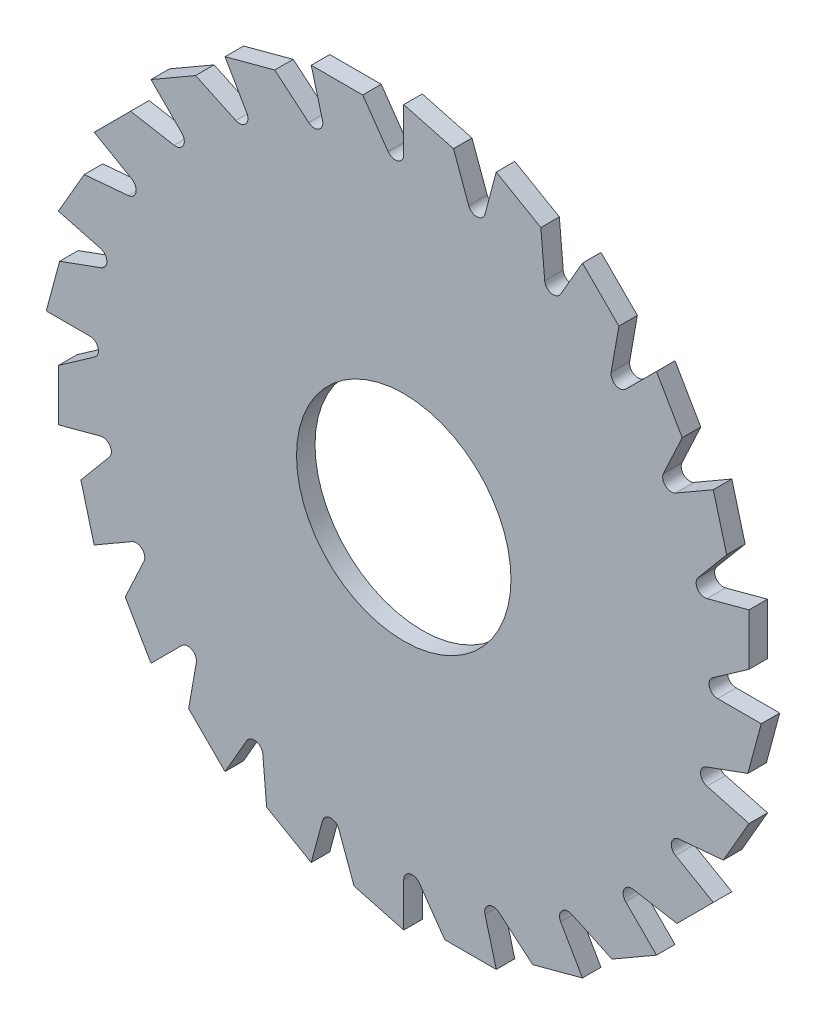
SolidWorks part; units mm, degrees
ref_plane "Front Plane" through (0, 0, 0) normal (0, 0, 1) x (1, 0, 0)
ref_plane "Top Plane" through (0, 0, 0) normal (0, 1, 0) x (1, 0, 0)
ref_plane "Right Plane" through (0, 0, 0) normal (1, 0, 0) x (0, 0, -1)
sketch "Sketch1" plane through (0, 0, 0) normal (0, 0, 1) x (1, 0, 0)
  line L0 (0, 31.75) -> (4.4162, 30.5667)
  line L1 (4.4162, 30.5667) -> (5.7634, 26.8652)
  line L2 (7.2155, 26.9286) -> (8.2175, 30.6681)
  line L3 (0, 31.75) -> (0, 0) construction
  line L4 (0, 0) -> (8.2175, 30.6681) construction
  line L5 (0, 31.75) -> (12.0811, 31.75) construction
  line L6 (6.3024, 26.3847) -> (0, 0) construction
  line L7 (6.3024, 26.3847) -> (4.0698, 26.918) construction
  line L8 (13.9393, 24.1436) -> (15.875, 27.4963)
  line L9 (12.177, 28.3821) -> (12.5203, 24.4581)
  line L10 (8.2175, 30.6681) -> (12.177, 28.3821)
  line L11 (19.7131, 19.7131) -> (22.4506, 22.4506)
  line L12 (19.1079, 24.2634) -> (18.4239, 20.3843)
  line L13 (15.875, 27.4963) -> (19.1079, 24.2634)
  line L14 (24.1436, 13.9393) -> (27.4963, 15.875)
  line L15 (24.7366, 18.4912) -> (23.072, 14.9212)
  line L16 (22.4506, 22.4506) -> (24.7366, 18.4912)
  line L17 (26.9286, 7.2155) -> (30.6681, 8.2175)
  line L18 (28.6796, 11.4588) -> (26.1477, 8.4413)
  line L19 (27.4963, 15.875) -> (28.6796, 11.4588)
  line L20 (27.8786, 0) -> (31.75, 0)
  line L21 (30.6681, 3.6455) -> (27.4415, 1.3862)
  line L22 (30.6681, 8.2175) -> (30.6681, 3.6455)
  line L23 (26.9286, -7.2155) -> (30.6681, -8.2175)
  line L24 (30.5667, -4.4162) -> (26.8652, -5.7634)
  line L25 (31.75, 0) -> (30.5667, -4.4162)
  line L26 (24.1436, -13.9393) -> (27.4963, -15.875)
  line L27 (28.3821, -12.177) -> (24.4581, -12.5203)
  line L28 (30.6681, -8.2175) -> (28.3821, -12.177)
  line L29 (19.7131, -19.7131) -> (22.4506, -22.4506)
  line L30 (24.2634, -19.1079) -> (20.3843, -18.4239)
  line L31 (27.4963, -15.875) -> (24.2634, -19.1079)
  line L32 (13.9393, -24.1436) -> (15.875, -27.4963)
  line L33 (18.4912, -24.7366) -> (14.9212, -23.072)
  line L34 (22.4506, -22.4506) -> (18.4912, -24.7366)
  line L35 (7.2155, -26.9286) -> (8.2175, -30.6681)
  line L36 (11.4588, -28.6796) -> (8.4413, -26.1477)
  line L37 (15.875, -27.4963) -> (11.4588, -28.6796)
  line L38 (0, -27.8786) -> (0, -31.75)
  line L39 (3.6455, -30.6681) -> (1.3862, -27.4415)
  line L40 (8.2175, -30.6681) -> (3.6455, -30.6681)
  line L41 (-7.2155, -26.9286) -> (-8.2175, -30.6681)
  line L42 (-4.4162, -30.5667) -> (-5.7634, -26.8652)
  line L43 (0, -31.75) -> (-4.4162, -30.5667)
  line L44 (-13.9393, -24.1436) -> (-15.875, -27.4963)
  line L45 (-12.177, -28.3821) -> (-12.5203, -24.4581)
  line L46 (-8.2175, -30.6681) -> (-12.177, -28.3821)
  line L47 (-19.7131, -19.7131) -> (-22.4506, -22.4506)
  line L48 (-19.1079, -24.2634) -> (-18.4239, -20.3843)
  line L49 (-15.875, -27.4963) -> (-19.1079, -24.2634)
  line L50 (-24.1436, -13.9393) -> (-27.4963, -15.875)
  line L51 (-24.7366, -18.4912) -> (-23.072, -14.9212)
  line L52 (-22.4506, -22.4506) -> (-24.7366, -18.4912)
  line L53 (-26.9286, -7.2155) -> (-30.6681, -8.2175)
  line L54 (-28.6796, -11.4588) -> (-26.1477, -8.4413)
  line L55 (-27.4963, -15.875) -> (-28.6796, -11.4588)
  line L56 (-27.8786, 0) -> (-31.75, 0)
  line L57 (-30.6681, -3.6455) -> (-27.4415, -1.3862)
  line L58 (-30.6681, -8.2175) -> (-30.6681, -3.6455)
  line L59 (-26.9286, 7.2155) -> (-30.6681, 8.2175)
  line L60 (-30.5667, 4.4162) -> (-26.8652, 5.7634)
  line L61 (-31.75, 0) -> (-30.5667, 4.4162)
  line L62 (-24.1436, 13.9393) -> (-27.4963, 15.875)
  line L63 (-28.3821, 12.177) -> (-24.4581, 12.5203)
  line L64 (-30.6681, 8.2175) -> (-28.3821, 12.177)
  line L65 (-19.7131, 19.7131) -> (-22.4506, 22.4506)
  line L66 (-24.2634, 19.1079) -> (-20.3843, 18.4239)
  line L67 (-27.4963, 15.875) -> (-24.2634, 19.1079)
  line L68 (-13.9393, 24.1436) -> (-15.875, 27.4963)
  line L69 (-18.4912, 24.7366) -> (-14.9212, 23.072)
  line L70 (-22.4506, 22.4506) -> (-18.4912, 24.7366)
  line L71 (-7.2155, 26.9286) -> (-8.2175, 30.6681)
  line L72 (-11.4588, 28.6796) -> (-8.4413, 26.1477)
  line L73 (-15.875, 27.4963) -> (-11.4588, 28.6796)
  line L74 (0, 27.8786) -> (0, 31.75)
  line L75 (-3.6455, 30.6681) -> (-1.3862, 27.4415)
  line L76 (-8.2175, 30.6681) -> (-3.6455, 30.6681)
  circle A0 centre (0, 0) radius 31.75 construction
  circle A1 centre (0, 0) radius 9.525
  circle A2 centre (0, 0) radius 27.127 construction
  arc A3 (5.7634, 26.8652) -> (7.2155, 26.9286) centre (6.4795, 27.1259) ccw
  arc A4 (12.5203, 24.4581) -> (13.9393, 24.1436) centre (13.2794, 24.5246) ccw
  arc A5 (18.4239, 20.3843) -> (19.7131, 19.7131) centre (19.1743, 20.2519) ccw
  arc A6 (23.072, 14.9212) -> (24.1436, 13.9393) centre (23.7626, 14.5992) ccw
  arc A7 (26.1477, 8.4413) -> (26.9286, 7.2155) centre (26.7314, 7.9515) ccw
  arc A8 (27.4415, 1.3862) -> (27.8786, 0) centre (27.8786, 0.762) ccw
  arc A9 (26.8652, -5.7634) -> (26.9286, -7.2155) centre (27.1259, -6.4795) ccw
  arc A10 (24.4581, -12.5203) -> (24.1436, -13.9393) centre (24.5246, -13.2794) ccw
  arc A11 (20.3843, -18.4239) -> (19.7131, -19.7131) centre (20.2519, -19.1743) ccw
  arc A12 (14.9212, -23.072) -> (13.9393, -24.1436) centre (14.5992, -23.7626) ccw
  arc A13 (8.4413, -26.1477) -> (7.2155, -26.9286) centre (7.9515, -26.7314) ccw
  arc A14 (1.3862, -27.4415) -> (0, -27.8786) centre (0.762, -27.8786) ccw
  arc A15 (-5.7634, -26.8652) -> (-7.2155, -26.9286) centre (-6.4795, -27.1259) ccw
  arc A16 (-12.5203, -24.4581) -> (-13.9393, -24.1436) centre (-13.2794, -24.5246) ccw
  arc A17 (-18.4239, -20.3843) -> (-19.7131, -19.7131) centre (-19.1743, -20.2519) ccw
  arc A18 (-23.072, -14.9212) -> (-24.1436, -13.9393) centre (-23.7626, -14.5992) ccw
  arc A19 (-26.1477, -8.4413) -> (-26.9286, -7.2155) centre (-26.7314, -7.9515) ccw
  arc A20 (-27.4415, -1.3862) -> (-27.8786, 0) centre (-27.8786, -0.762) ccw
  arc A21 (-26.8652, 5.7634) -> (-26.9286, 7.2155) centre (-27.1259, 6.4795) ccw
  arc A22 (-24.4581, 12.5203) -> (-24.1436, 13.9393) centre (-24.5246, 13.2794) ccw
  arc A23 (-20.3843, 18.4239) -> (-19.7131, 19.7131) centre (-20.2519, 19.1743) ccw
  arc A24 (-14.9212, 23.072) -> (-13.9393, 24.1436) centre (-14.5992, 23.7626) ccw
  arc A25 (-8.4413, 26.1477) -> (-7.2155, 26.9286) centre (-7.9515, 26.7314) ccw
  arc A26 (-1.3862, 27.4415) -> (0, 27.8786) centre (-0.762, 27.8786) ccw
  dimension "D1" = 63.5
  dimension "D2" = 19.05
  dimension "D3" = 125
  dimension "D7" = 0.762
  dimension "D4" = 15
  dimension "D5" = 15
  dimension "D6" = 4.572
  dimension "D8" = 24
extrude "Boss-Extrude1" add sketch "Sketch1" along normal blind 1.6444 contours A26 L75 L76 L71 A25 L72 L73 L68 A24 L69 L70 L65 A23 L66 L67 L62 A22 L63 L64 L59 A21 L60 L61 L56 A20 L57 L58 L53 A19 L54 L55 L50 A18 L51 L52 L47 A17 L48 L49 L44 A16 L45 L46 L41 A15 L42 L43 L38 A14 L39 L40 region at (1.9757, 30.2909, 0)
ref_plane "Plane1" through (0, 0, 0.8222) normal (0, 0, 1) x (1, 0, 0)
sketch "Sketch2" plane through (0, 0, 0) normal (0, 0, 1) x (1, 0, 0)
  line L0 (31.75, -31.75) -> (31.75, 31.75)
  line L1 (400.05, -31.75) -> (-31.75, -31.75)
  line L2 (400.05, -31.75) -> (400.05, 400.05)
  line L3 (400.05, 400.05) -> (-31.75, 400.05)
  line L4 (-31.75, -31.75) -> (-31.75, 400.05)
  line L5 (184.15, 400.05) -> (184.15, -31.75) construction
  line L6 (400.05, 184.15) -> (-31.75, 184.15) construction
  line L7 (-31.75, -31.75) -> (31.75, -31.75)
  line L8 (-31.75, -31.75) -> (-31.75, 31.75)
  line L9 (-31.75, 31.75) -> (31.75, 31.75)
  line L10 (31.75, -31.75) -> (31.75, 31.75)
  line L11 (0, 31.75) -> (0, -31.75) construction
  line L12 (-31.75, 0) -> (31.75, 0) construction
  line L13 (31.75, -31.75) -> (95.25, -31.75)
  line L14 (95.25, -31.75) -> (95.25, 31.75)
  line L15 (31.75, 31.75) -> (95.25, 31.75)
  line L16 (95.25, -31.75) -> (95.25, 31.75)
  line L17 (95.25, -31.75) -> (158.75, -31.75)
  line L18 (158.75, -31.75) -> (158.75, 31.75)
  line L19 (95.25, 31.75) -> (158.75, 31.75)
  line L20 (158.75, -31.75) -> (158.75, 31.75)
  line L21 (158.75, -31.75) -> (222.25, -31.75)
  line L22 (222.25, -31.75) -> (222.25, 31.75)
  line L23 (158.75, 31.75) -> (222.25, 31.75)
  line L24 (222.25, -31.75) -> (222.25, 31.75)
  line L25 (222.25, -31.75) -> (285.75, -31.75)
  line L26 (285.75, -31.75) -> (285.75, 31.75)
  line L27 (222.25, 31.75) -> (285.75, 31.75)
  line L28 (285.75, -31.75) -> (285.75, 31.75)
  line L29 (285.75, -31.75) -> (349.25, -31.75)
  line L30 (349.25, -31.75) -> (349.25, 31.75)
  line L31 (285.75, 31.75) -> (349.25, 31.75)
  line L32 (31.75, 31.75) -> (31.75, 95.25)
  line L33 (31.75, 31.75) -> (95.25, 31.75)
  line L34 (95.25, 31.75) -> (95.25, 95.25)
  line L35 (31.75, 95.25) -> (95.25, 95.25)
  line L36 (95.25, 31.75) -> (95.25, 95.25)
  line L37 (95.25, 31.75) -> (158.75, 31.75)
  line L38 (158.75, 31.75) -> (158.75, 95.25)
  line L39 (95.25, 95.25) -> (158.75, 95.25)
  line L40 (158.75, 31.75) -> (158.75, 95.25)
  line L41 (158.75, 31.75) -> (222.25, 31.75)
  line L42 (222.25, 31.75) -> (222.25, 95.25)
  line L43 (158.75, 95.25) -> (222.25, 95.25)
  line L44 (222.25, 31.75) -> (222.25, 95.25)
  line L45 (222.25, 31.75) -> (285.75, 31.75)
  line L46 (285.75, 31.75) -> (285.75, 95.25)
  line L47 (222.25, 95.25) -> (285.75, 95.25)
  line L48 (285.75, 31.75) -> (285.75, 95.25)
  line L49 (285.75, 31.75) -> (349.25, 31.75)
  line L50 (349.25, 31.75) -> (349.25, 95.25)
  line L51 (285.75, 95.25) -> (349.25, 95.25)
  line L52 (31.75, 95.25) -> (31.75, 158.75)
  line L53 (31.75, 95.25) -> (95.25, 95.25)
  line L54 (95.25, 95.25) -> (95.25, 158.75)
  line L55 (31.75, 158.75) -> (95.25, 158.75)
  line L56 (95.25, 95.25) -> (95.25, 158.75)
  line L57 (95.25, 95.25) -> (158.75, 95.25)
  line L58 (158.75, 95.25) -> (158.75, 158.75)
  line L59 (95.25, 158.75) -> (158.75, 158.75)
  line L60 (158.75, 95.25) -> (158.75, 158.75)
  line L61 (158.75, 95.25) -> (222.25, 95.25)
  line L62 (222.25, 95.25) -> (222.25, 158.75)
  line L63 (158.75, 158.75) -> (222.25, 158.75)
  line L64 (222.25, 95.25) -> (222.25, 158.75)
  line L65 (222.25, 95.25) -> (285.75, 95.25)
  line L66 (285.75, 95.25) -> (285.75, 158.75)
  line L67 (222.25, 158.75) -> (285.75, 158.75)
  line L68 (285.75, 95.25) -> (285.75, 158.75)
  line L69 (285.75, 95.25) -> (349.25, 95.25)
  line L70 (349.25, 95.25) -> (349.25, 158.75)
  line L71 (285.75, 158.75) -> (349.25, 158.75)
  line L72 (31.75, 158.75) -> (31.75, 222.25)
  line L73 (31.75, 158.75) -> (95.25, 158.75)
  line L74 (95.25, 158.75) -> (95.25, 222.25)
  line L75 (31.75, 222.25) -> (95.25, 222.25)
  line L76 (95.25, 158.75) -> (95.25, 222.25)
  line L77 (95.25, 158.75) -> (158.75, 158.75)
  line L78 (158.75, 158.75) -> (158.75, 222.25)
  line L79 (95.25, 222.25) -> (158.75, 222.25)
  line L80 (158.75, 158.75) -> (158.75, 222.25)
  line L81 (158.75, 158.75) -> (222.25, 158.75)
  line L82 (222.25, 158.75) -> (222.25, 222.25)
  line L83 (158.75, 222.25) -> (222.25, 222.25)
  line L84 (222.25, 158.75) -> (222.25, 222.25)
  line L85 (222.25, 158.75) -> (285.75, 158.75)
  line L86 (285.75, 158.75) -> (285.75, 222.25)
  line L87 (222.25, 222.25) -> (285.75, 222.25)
  line L88 (285.75, 158.75) -> (285.75, 222.25)
  line L89 (285.75, 158.75) -> (349.25, 158.75)
  line L90 (349.25, 158.75) -> (349.25, 222.25)
  line L91 (285.75, 222.25) -> (349.25, 222.25)
  line L92 (31.75, 222.25) -> (31.75, 285.75)
  line L93 (31.75, 222.25) -> (95.25, 222.25)
  line L94 (95.25, 222.25) -> (95.25, 285.75)
  line L95 (31.75, 285.75) -> (95.25, 285.75)
  line L96 (95.25, 222.25) -> (95.25, 285.75)
  line L97 (95.25, 222.25) -> (158.75, 222.25)
  line L98 (158.75, 222.25) -> (158.75, 285.75)
  line L99 (95.25, 285.75) -> (158.75, 285.75)
  line L100 (158.75, 222.25) -> (158.75, 285.75)
  line L101 (158.75, 222.25) -> (222.25, 222.25)
  line L102 (222.25, 222.25) -> (222.25, 285.75)
  line L103 (158.75, 285.75) -> (222.25, 285.75)
  line L104 (222.25, 222.25) -> (222.25, 285.75)
  line L105 (222.25, 222.25) -> (285.75, 222.25)
  line L106 (285.75, 222.25) -> (285.75, 285.75)
  line L107 (222.25, 285.75) -> (285.75, 285.75)
  line L108 (285.75, 222.25) -> (285.75, 285.75)
  line L109 (285.75, 222.25) -> (349.25, 222.25)
  line L110 (349.25, 222.25) -> (349.25, 285.75)
  line L111 (285.75, 285.75) -> (349.25, 285.75)
  line L112 (31.75, 285.75) -> (31.75, 349.25)
  line L113 (31.75, 285.75) -> (95.25, 285.75)
  line L114 (95.25, 285.75) -> (95.25, 349.25)
  line L115 (31.75, 349.25) -> (95.25, 349.25)
  line L116 (95.25, 285.75) -> (95.25, 349.25)
  line L117 (95.25, 285.75) -> (158.75, 285.75)
  line L118 (158.75, 285.75) -> (158.75, 349.25)
  line L119 (95.25, 349.25) -> (158.75, 349.25)
  line L120 (158.75, 285.75) -> (158.75, 349.25)
  line L121 (158.75, 285.75) -> (222.25, 285.75)
  line L122 (222.25, 285.75) -> (222.25, 349.25)
  line L123 (158.75, 349.25) -> (222.25, 349.25)
  line L124 (222.25, 285.75) -> (222.25, 349.25)
  line L125 (222.25, 285.75) -> (285.75, 285.75)
  line L126 (285.75, 285.75) -> (285.75, 349.25)
  line L127 (222.25, 349.25) -> (285.75, 349.25)
  line L128 (285.75, 285.75) -> (285.75, 349.25)
  line L129 (285.75, 285.75) -> (349.25, 285.75)
  line L130 (349.25, 285.75) -> (349.25, 349.25)
  line L131 (285.75, 349.25) -> (349.25, 349.25)
  line L132 (-31.75, 31.75) -> (-31.75, 95.25)
  line L133 (-31.75, 31.75) -> (31.75, 31.75)
  line L134 (31.75, 31.75) -> (31.75, 95.25)
  line L135 (-31.75, 95.25) -> (31.75, 95.25)
  line L136 (-31.75, 95.25) -> (-31.75, 158.75)
  line L137 (-31.75, 95.25) -> (31.75, 95.25)
  line L138 (31.75, 95.25) -> (31.75, 158.75)
  line L139 (-31.75, 158.75) -> (31.75, 158.75)
  line L140 (-31.75, 158.75) -> (-31.75, 222.25)
  line L141 (-31.75, 158.75) -> (31.75, 158.75)
  line L142 (31.75, 158.75) -> (31.75, 222.25)
  line L143 (-31.75, 222.25) -> (31.75, 222.25)
  line L144 (-31.75, 222.25) -> (-31.75, 285.75)
  line L145 (-31.75, 222.25) -> (31.75, 222.25)
  line L146 (31.75, 222.25) -> (31.75, 285.75)
  line L147 (-31.75, 285.75) -> (31.75, 285.75)
  line L148 (-31.75, 285.75) -> (-31.75, 349.25)
  line L149 (-31.75, 285.75) -> (31.75, 285.75)
  line L150 (31.75, 285.75) -> (31.75, 349.25)
  line L151 (-31.75, 349.25) -> (31.75, 349.25)
  line L152 (-31.75, -31.75) -> (31.75, -31.75) construction
  line L153 (-31.75, -31.75) -> (-31.75, 31.75) construction
  line L155 (-31.75, 400.05) -> (57.15, 400.05)
  line L156 (-31.75, 400.05) -> (-31.75, 349.25)
  line L157 (-31.75, 349.25) -> (57.15, 349.25)
  line L158 (57.15, 400.05) -> (57.15, 349.25)
  line L159 (57.15, 400.05) -> (146.05, 400.05)
  line L160 (57.15, 400.05) -> (57.15, 349.25)
  line L161 (57.15, 349.25) -> (146.05, 349.25)
  line L162 (146.05, 400.05) -> (146.05, 349.25)
  line L163 (146.05, 400.05) -> (234.95, 400.05)
  line L164 (146.05, 400.05) -> (146.05, 349.25)
  line L165 (146.05, 349.25) -> (234.95, 349.25)
  line L166 (234.95, 400.05) -> (234.95, 349.25)
  line L167 (234.95, 400.05) -> (323.85, 400.05)
  line L168 (234.95, 400.05) -> (234.95, 349.25)
  line L169 (234.95, 349.25) -> (323.85, 349.25)
  line L170 (323.85, 400.05) -> (323.85, 349.25)
  point P0 (184.15, 184.15)
  point P4 (0, 0)
  dimension "D1" = 431.8
  dimension "D2" = 431.8
  dimension "D3" = 63.5
  dimension "D4" = 6
  dimension "D6" = 63.5
  dimension "D7" = 63.5
  dimension "D8" = 88.9
  dimension "D9" = 88.9
  dimension "D10" = 88.9
  dimension "D11" = 88.9
  dimension "D5" = 6
equation "\"AVRG_T_Sprocket\"= ( 10 * 2 + 8 * 1.2 ) / 18mm"
equation "\"AVRG_T_NoSprocket\"= ( 9 * 2 + 8 * 1.2 ) / 18mm"
equation "\"D1@Boss-Extrude1\"  = \"AVRG_T_Sprocket\""
